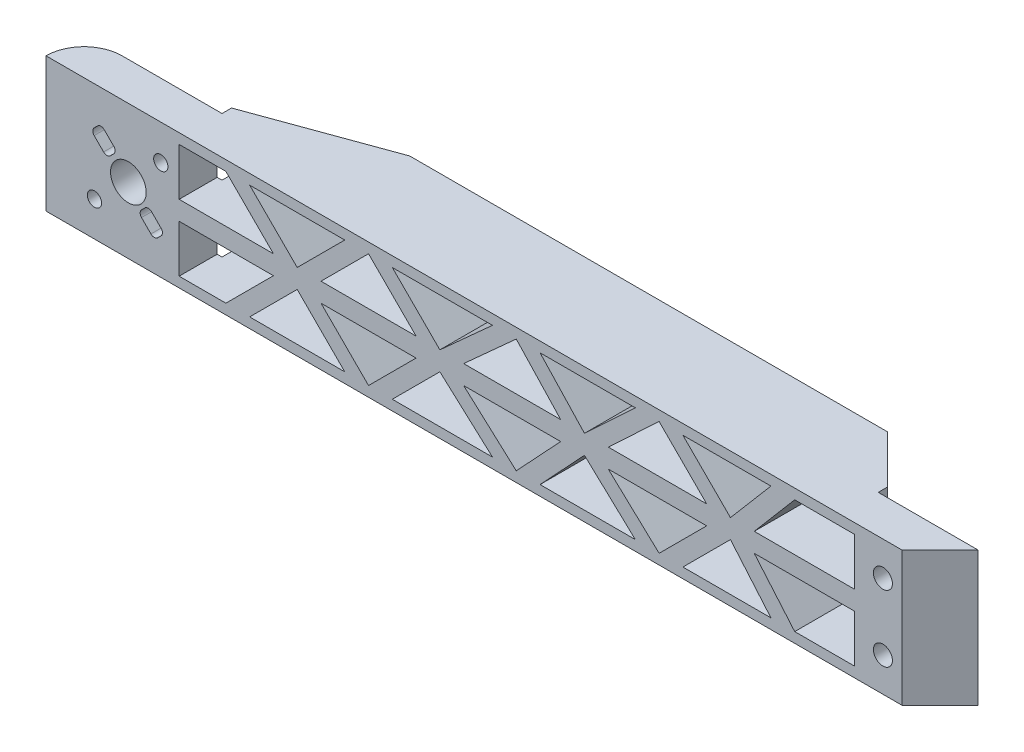
SolidWorks part; units mm, degrees
ref_plane "Plan de face" through (0, 0, 0) normal (0, 0, 1) x (1, 0, 0)
ref_plane "Plan de dessus" through (0, 0, 0) normal (0, 1, 0) x (1, 0, 0)
ref_plane "Plan de droite" through (0, 0, 0) normal (1, 0, 0) x (0, 0, -1)
sketch "Esquisse1" plane through (0, 0, 0) normal (0, 0, 1) x (1, 0, 0)
  line L1 (0, 0) -> (200, 0)
  line L2 (0, 0) -> (0, 28.284)
  line L3 (0, 28.284) -> (200, 28.284)
  line L4 (200, 0) -> (200, 28.284)
  dimension "D1" = 200
  dimension "D2" = 28.284
extrude "Boss.-Extru.3" add sketch "Esquisse1" along normal blind 8
chamfer "Chanfrein1" distance 20 angle 45 1 edges at (200, 14.142, 8)
sketch "Esquisse4" plane through (0, 0, 8) normal (0, 0, 1) x (1, 0, 0)
  line L0 (0, 0) -> (180, 0) construction
  line L2 (180, 0) -> (180, 28.284) construction
  line L5 (180, 28.284) -> (0, 28.284) construction
  circle A0 centre (176, 7.142) radius 2
  circle A1 centre (176, 21.142) radius 2
  dimension "D3" = 4
  dimension "D4" = 4
  dimension "D1" = 7.142
  dimension "D2" = 7.142
  dimension "D5" = 4
  dimension "D6" = 4
extrude "Cut-Extrude5" cut sketch "Esquisse4" against normal blind 30
fillet "Fillet1" radius 8 1 edges at (0, 14.142, 0)
sketch "Sketch2" plane through (0, 0, 8) normal (0, 0, 1) x (1, 0, 0)
  line L4 (14.9435, 18.2434) -> (12.8222, 16.122)
  line L6 (19.3798, 9.5645) -> (22.78, 6.1646)
  line L9 (12.8222, 16.122) -> (9.4222, 19.522)
  line L11 (11.5435, 21.6434) -> (14.9435, 18.2434)
  line L16 (22.78, 6.1646) -> (24.9012, 8.286)
  line L24 (9.4222, 19.522) -> (11.5435, 21.6434)
  line L26 (24.9012, 8.286) -> (21.5011, 11.6858)
  line L27 (21.5011, 11.6858) -> (19.3798, 9.5645)
  circle A0 centre (10.1805, 7.2815) radius 1.5
  circle A3 centre (24.1429, 20.8833) radius 1.5
  circle A4 centre (17.323, 13.9183) radius 3.75
  dimension "D4" = 3
  dimension "D6" = 3
  dimension "D3" = 7.5
  dimension "D1" = 9.75
  dimension "D9" = 19.4925
extrude "Cut-Extrude1" cut sketch "Sketch2" against normal blind 8
fillet "Fillet9" radius 1 4 edges at (9.4222, 19.522, 4) (11.5435, 21.6434, 4) (12.8222, 16.122, 4) (14.9435, 18.2434, 4)
fillet "Fillet10" radius 1 4 edges at (24.9012, 8.286, 4) (22.78, 6.1646, 4) (21.5011, 11.6858, 4) (19.3798, 9.5645, 4)
sketch "Sketch3" plane through (0, 0, 8) normal (0, 0, 1) x (1, 0, 0)
  circle A0 centre (17.5366, 14.6901) radius 2.1502
sketch "Sketch4" plane through (0, 0, 8) normal (0, 0, 1) x (1, 0, 0)
  line L0 (28, 26.144) -> (28, 2.144)
  line L1 (28, 2.144) -> (170, 2.144)
  line L2 (170, 2.144) -> (170, 26.144)
  line L3 (170, 26.144) -> (28, 26.144)
  line L4 (180, 28.284) -> (0, 28.284) construction
  line L5 (82.8289, 12.144) -> (72.8289, 2.144)
  line L6 (77.8289, 12.144) -> (67.8289, 2.144)
  line L7 (67.8289, 2.144) -> (57.8289, 12.144)
  line L8 (0, 28.284) -> (0, 0) construction
  line L9 (28, 16.144) -> (170, 16.144)
  line L10 (28, 12.144) -> (170, 12.144)
  line L11 (62.8289, 2.144) -> (52.8289, 12.144)
  line L12 (52.8289, 12.144) -> (42.8289, 2.144)
  line L13 (47.8289, 12.144) -> (37.8289, 2.144)
  line L14 (87.8289, 12.144) -> (98.8946, 2.144)
  line L15 (82.8289, 12.144) -> (93.8946, 2.144)
  line L16 (98.8946, 2.144) -> (108.2382, 12.144)
  line L17 (113.2382, 12.144) -> (103.8946, 2.144)
  line L18 (113.2382, 12.144) -> (123.9407, 2.144)
  line L19 (128.9407, 2.144) -> (118.2382, 12.144)
  line L20 (128.9407, 2.144) -> (138.9407, 12.144)
  line L21 (133.9407, 2.144) -> (143.9407, 12.144)
  line L22 (143.9407, 12.144) -> (152.4557, 2.144)
  line L23 (157.4557, 2.144) -> (148.9407, 12.144)
  line L24 (143.9407, 12.144) -> (143.9407, 16.144)
  line L26 (148.9407, 12.144) -> (148.9407, 16.144)
  line L27 (138.9407, 12.144) -> (138.9407, 16.144)
  line L29 (148.9407, 16.144) -> (157.4557, 26.144)
  line L31 (143.9407, 16.144) -> (152.4557, 26.144)
  line L33 (138.9407, 16.144) -> (128.9407, 26.144)
  line L34 (143.9407, 16.144) -> (133.9407, 26.144)
  line L35 (128.9407, 26.144) -> (118.2382, 16.144)
  line L36 (157.4557, 26.144) -> (157.4557, 28.284)
  line L37 (113.2382, 16.144) -> (123.9407, 26.144)
  line L38 (113.2382, 16.144) -> (103.8946, 26.144)
  line L40 (108.2382, 12.144) -> (108.2382, 16.144)
  line L42 (108.2382, 16.144) -> (98.8946, 26.144)
  line L44 (98.8946, 26.144) -> (87.8289, 16.144)
  line L45 (180, 28.284) -> (0, 28.284) construction
  line L46 (82.8289, 16.144) -> (93.8946, 26.144)
  line L48 (82.8289, 16.144) -> (72.8289, 26.144)
  line L49 (77.8289, 16.144) -> (67.8289, 26.144)
  line L52 (152.4557, 26.144) -> (152.4557, 28.284)
  line L54 (67.8289, 26.144) -> (57.8289, 16.144)
  line L55 (52.8289, 16.144) -> (62.8289, 26.144)
  line L57 (52.8289, 16.144) -> (42.8289, 26.144)
  line L59 (42.8289, 26.144) -> (62.8289, 26.144)
  line L60 (57.8289, 16.144) -> (77.8289, 16.144)
  line L61 (72.8289, 26.144) -> (93.8946, 26.144)
  line L62 (87.8289, 16.144) -> (108.2382, 16.144)
  line L63 (103.8946, 26.144) -> (123.9407, 26.144)
  line L64 (118.2382, 16.144) -> (138.9407, 16.144)
  line L65 (133.9407, 26.144) -> (152.4557, 26.144)
  line L66 (157.4557, 26.144) -> (170, 26.144)
  line L67 (170, 16.144) -> (170, 26.144)
  line L68 (148.9407, 16.144) -> (170, 16.144)
  line L69 (28, 26.144) -> (37.8289, 26.144)
  line L70 (28, 16.144) -> (28, 26.144)
  line L71 (28, 16.144) -> (47.8289, 16.144)
  line L72 (37.8289, 26.144) -> (28, 26.144)
  line L73 (28, 16.144) -> (47.8289, 16.144)
  line L74 (28, 26.144) -> (28, 16.144)
  line L75 (28, 16.144) -> (47.8289, 16.144)
  line L76 (37.8289, 26.144) -> (28, 26.144)
  line L77 (28, 26.144) -> (37.8289, 26.144)
  line L78 (133.9407, 26.144) -> (133.9407, 28.284)
  line L79 (28, 16.144) -> (28, 26.144)
  line L80 (37.8289, 26.144) -> (28, 26.144)
  line L81 (28, 16.144) -> (47.8289, 16.144)
  line L82 (128.9407, 26.144) -> (128.9407, 28.284)
  line L83 (123.9407, 26.144) -> (123.9407, 28.284)
  line L84 (28, 16.144) -> (47.8289, 16.144)
  line L85 (37.8289, 26.144) -> (47.8289, 16.144)
  line L86 (37.9145, 14.5675) -> (37.9145, 14.3901)
  line L87 (28, 26.144) -> (28, 16.144)
  line L88 (47.8289, 16.144) -> (28, 16.144)
  line L89 (28, 26.144) -> (37.8289, 26.144)
  line L90 (37.8289, 26.144) -> (47.8289, 16.144)
  line L91 (103.8946, 26.144) -> (103.8946, 28.284)
  line L92 (98.8946, 26.144) -> (98.8946, 28.284)
  line L93 (93.8946, 26.144) -> (93.8946, 28.284)
  line L94 (72.8289, 26.144) -> (72.8289, 28.284)
  line L95 (67.8289, 26.144) -> (67.8289, 28.284)
  line L96 (62.8289, 26.144) -> (62.8289, 28.284)
  line L97 (42.8289, 26.144) -> (42.8289, 28.284)
  line L98 (37.8289, 26.144) -> (37.8289, 28.284)
  line L99 (37.8289, 2.144) -> (37.8289, 0)
  line L100 (0, 0) -> (180, 0) construction
  line L101 (42.8289, 2.144) -> (42.8289, 0)
  line L102 (62.8289, 2.144) -> (62.8289, 0)
  line L103 (67.8289, 2.144) -> (67.8289, 0)
  line L104 (72.8289, 2.144) -> (72.8289, 0)
  line L105 (103.8946, 2.144) -> (103.8946, 0)
  line L106 (98.8946, 2.144) -> (98.8946, 0)
  line L107 (93.8946, 2.144) -> (93.8946, 0)
  line L108 (133.9407, 2.144) -> (133.9407, 0)
  line L109 (128.9407, 2.144) -> (128.9407, 0)
  line L110 (123.9407, 2.144) -> (123.9407, 0)
  line L111 (157.4557, 2.144) -> (157.4557, 0)
  line L112 (152.4557, 2.144) -> (152.4557, 0)
  dimension "D1" = 2.14
  dimension "D2" = 24
  dimension "D3" = 142
  dimension "D4" = 28
  dimension "D5" = 10
  dimension "D6" = 10
  dimension "D7" = 5
  dimension "D8" = 5
  dimension "D9" = 5
  dimension "D10" = 5
  dimension "D11" = 5
  dimension "D12" = 5
  dimension "D13" = 5
  dimension "D14" = 5
  dimension "D15" = 5
  dimension "D16" = 5
  dimension "D17" = 5
  dimension "D18" = 5
  dimension "D19" = 5
  dimension "D20" = 5
  dimension "D21" = 5
  dimension "D22" = 5
  dimension "D23" = 5
  dimension "D24" = 5
sketch "Sketch6" plane through (0, 0, 0) normal (0, 0, -1) x (-1, 0, 0)
  line L0 (-167.0182, 0) -> (-167.0182, 28.284)
  line L1 (-8, 0) -> (-188, 0) construction
  line L2 (-188, 28.284) -> (-8, 28.284) construction
  line L3 (-167.0182, 28.284) -> (-29.0182, 28.284)
  line L4 (-29.0182, 28.284) -> (-29.0182, 0)
  line L5 (-29.0182, 0) -> (-167.0182, 0)
  dimension "D1" = 138
  dimension "D2" = 21.0182
extrude "Boss-Extrude3" add sketch "Sketch6" along normal blind 12
chamfer "Chamfer2" distance 10 angle 70 1 edges at (29.0182, 14.142, -12) first distance on face at (29.0182, 14.142, -6)
extrude "Cut-Extrude6" cut sketch "Sketch4" against normal blind 20 contours L13 L10 L0 L1 | L11 L12 L1 | L10 L7 L6 | L15 L5 L1 | L14 L16 L10 | L18 L17 L1 | L19 L20 L10 | L22 L21 L1 | L23 L1 L2 L10 | L29 L9 L2 L3 | L34 L31 L3 | L33 L35 L9 | L38 L37 L3 | L42 L44 L9 | L48 L46 L3 | L49 L54 L9 | L57 L55 L3 | L85 L3 L0 L9 region at (35.6954, 20.582, 8) region at (35.6954, 7.706, 8) region at (52.8289, 22.8107, 8) region at (52.8289, 5.4773, 8) region at (67.8289, 19.4773, 8) region at (67.8289, 8.8107, 8) region at (83.1841, 22.8107, 8) region at (83.1841, 5.4773, 8) region at (98.3206, 19.4773, 8) region at (98.3206, 8.8107, 8) region at (113.6912, 22.8107, 8) region at (113.6912, 5.4773, 8) region at (128.7065, 19.4773, 8) region at (128.7065, 8.8107, 8) region at (143.4457, 22.8107, 8) region at (143.4457, 5.4773, 8) region at (161.4193, 20.7217, 8) region at (161.4193, 7.5663, 8)
chamfer "Chamfer8" distance 10 angle 45 2 edges at (167.0182, 1.072, -12) (167.0182, 14.144, -12)
chamfer "Chamfer9" distance 10 angle 45 1 edges at (167.0182, 27.214, -12)
sketch "Sketch7" plane through (0, 0, 0) normal (0, -1, 0) x (-1, 0, 0)
  line L0 (-1.0718, -4) -> (-184, -4)
  line L3 (-188, 0) -> (-180, -8) construction
  line L4 (-52.8289, -8) -> (-42.8289, -8) construction
  line L5 (-34.5132, 4) -> (-165.0182, 4)
  line L6 (-29.0182, 2) -> (-56.493, 12) construction
  line L7 (-157.0182, 12) -> (-167.0182, 2) construction
  line L8 (-29.0182, 0) -> (-167.0182, 0)
  arc A0 (0, -8) -> (-8, 0) centre (-8, -8) ccw construction
  point P10 (-47.8289, -8)
  dimension "D1" = 4
